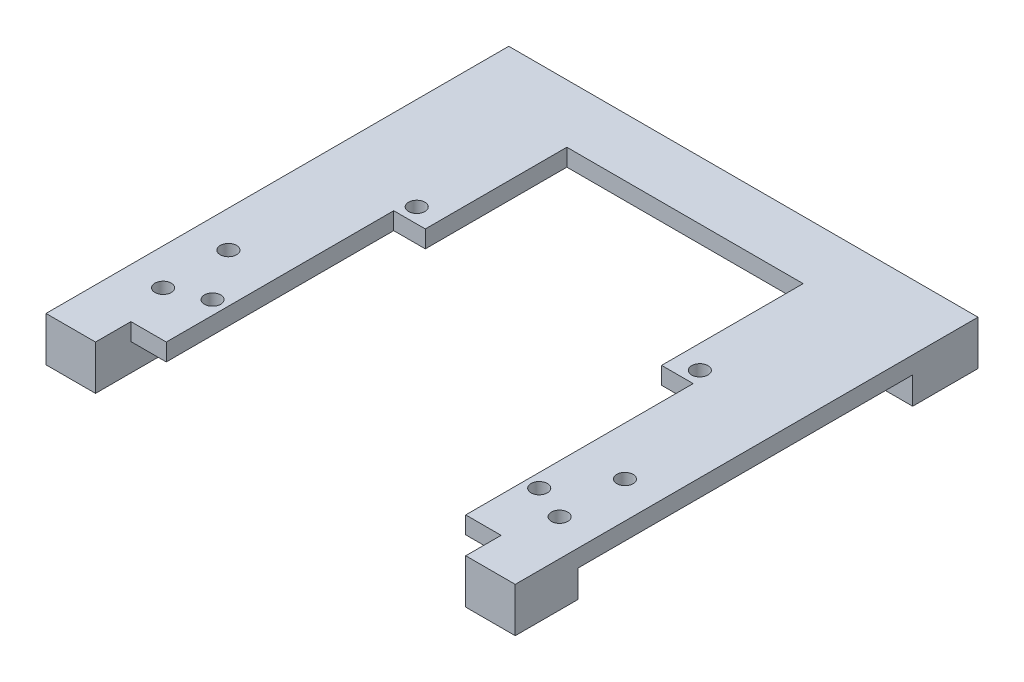
SolidWorks part; units mm, degrees
material "6061 Alloy"
ref_plane "Front Plane" through (0, 0, 0) normal (0, 0, 1) x (1, 0, 0)
ref_plane "Top Plane" through (0, 0, 0) normal (0, 1, 0) x (1, 0, 0)
ref_plane "Right Plane" through (0, 0, 0) normal (1, 0, 0) x (0, 0, -1)
sketch "Sketch1" plane through (0, 0, 0) normal (0, 1, 0) x (1, 0, 0)
  line L0 (0, 0) -> (0, -58.55) construction
  line L1 (-83.4462, -16.178) -> (-71.2857, -8.5793) construction
  line L6 (0, 0) -> (-59.046, 61.1439) construction
  line L7 (0, 0) -> (-72.0841, -45.0431) construction
  line L8 (-33.174, 78.2591) -> (-23.2129, 67.9442) construction
  line L9 (-72.0841, -45.0431) -> (-70.388, -43.9833) construction
  line L10 (-70.388, -43.9833) -> (-84.9608, -20.662) construction
  line L11 (-84.9608, -20.662) -> (-72.2401, -12.7132) construction
  line L12 (-72.2401, -12.7132) -> (-43.0945, -59.3558) construction
  line L13 (-43.0945, -59.3558) -> (-55.8152, -67.3046) construction
  line L14 (-55.8152, -67.3046) -> (-70.388, -43.9833) construction
  line L21 (-59.046, 61.1439) -> (-57.6566, 59.7052)
  line L22 (-77.4385, 40.6021) -> (-37.8748, 78.8083) construction
  line L23 (-73.9694, 32.6911) -> (-77.0537, 35.885)
  line L24 (-37.8748, 78.8083) -> (-27.4549, 68.0182) construction
  line L25 (-27.4549, 68.0182) -> (-67.0186, 29.812) construction
  line L26 (-67.0186, 29.812) -> (-77.4385, 40.6021) construction
  line L27 (-43.0945, -64.8266) -> (-34, -64.8266)
  line L33 (-86.5505, -18.1178) -> (-71.2857, -8.5793) construction
  line L34 (0, 0) -> (0, 50000) construction
  line L35 (0, 0) -> (-50000, 0) construction
  line L36 (-61.619, -58.55) -> (0, -58.55) construction
  line L38 (-67.0927, 25.57) -> (-79.5965, 38.5181) construction
  line L39 (-54.9774, -64.8266) -> (0, -64.8266) construction
  line L40 (-35.7168, 80.8923) -> (-23.2129, 67.9442) construction
  line L41 (-38.9606, -60.3102) -> (-54.2255, -69.8488) construction
  line L42 (-34, -58.55) -> (34, -58.55) construction
  line L43 (-43.0945, -64.8266) -> (-43.0945, -58.4123)
  line L45 (73.9694, 32.6911) -> (77.0537, 35.885)
  line L46 (-71.2857, -8.5793) -> (-38.9606, -60.3102) construction
  line L47 (83.4462, -16.178) -> (79.6809, -13.8252)
  line L48 (69.4846, -16.1792) -> (43.0945, -58.4123)
  line L49 (43.0945, -64.8266) -> (43.0945, -58.4123)
  line L50 (43.0945, -64.8266) -> (34, -64.8266)
  line L51 (34, -58.55) -> (34, -64.8266)
  line L52 (0, 0) -> (72.0841, -45.0431) construction
  line L53 (0, 0) -> (59.046, 61.1439) construction
  line L54 (-30.0897, 75.0653) -> (-30.2847, 63.8954)
  line L55 (-62.7996, 32.4961) -> (-30.2847, 63.8954)
  line L56 (-30.0897, 75.0653) -> (-33.174, 78.2591)
  line L57 (73.9694, 32.6911) -> (77.0537, 35.885)
  line L58 (30.0897, 75.0653) -> (33.174, 78.2591)
  line L59 (-34, -58.55) -> (-34, -53.55)
  line L60 (62.7996, 32.4961) -> (30.2847, 63.8954)
  line L61 (-73.9694, 32.6911) -> (-62.7996, 32.4961)
  line L62 (-77.0537, 35.885) -> (-67.0927, 25.57) construction
  line L63 (-83.4462, -16.178) -> (-79.6809, -13.8252)
  line L64 (-79.6809, -13.8252) -> (-69.4846, -16.1792)
  line L65 (-69.4846, -16.1792) -> (-43.0945, -58.4123)
  line L66 (-27.4549, 68.0182) -> (-23.2129, 67.9442) construction
  line L67 (-72.2401, -12.7132) -> (-71.2857, -8.5793) construction
  line L68 (30.0897, 75.0653) -> (30.2847, 63.8954)
  line L69 (73.9694, 32.6911) -> (62.7996, 32.4961)
  line L70 (-34, -58.55) -> (-34, -64.8266)
  line L71 (79.6809, -13.8252) -> (69.4846, -16.1792)
  line L72 (-34, -53.55) -> (-28, -53.55)
  line L73 (-28, -53.55) -> (-28, -58.55)
  line L74 (-28, -58.55) -> (28, -58.55)
  line L75 (28, -53.55) -> (28, -58.55)
  line L76 (34, -53.55) -> (28, -53.55)
  line L77 (34, -58.55) -> (34, -53.55)
  line L78 (-34, -58.55) -> (-28, -58.55)
  line L79 (28, -58.55) -> (34, -58.55)
  line L97 (-23.2129, 67.9442) -> (-67.0927, 25.57) construction
  circle A0 centre (0, 0) radius 85 construction
  circle A1 centre (0, 0) radius 90 construction
  arc A51 (-77.0537, 35.885) -> (-83.4462, -16.178) centre (0, 0) ccw
  arc A52 (77.0537, 35.885) -> (83.4462, -16.178) centre (0, 0) cw
  arc A54 (-33.174, 78.2591) -> (33.174, 78.2591) centre (0, 0) cw
  point P29 (-31.6318, 76.6622)
  point P33 (-47.2368, 48.9151)
  point P34 (31.6318, 76.6622)
  point P35 (-57.6673, -36.0345)
  point P85 (-57.6566, 59.7052)
  dimension "D2" = 58
  dimension "D12" = 170
  dimension "D14" = 34
  dimension "D15" = 3
  dimension "D3" = 180
  dimension "D4" = 64.8266
  dimension "D5" = 44
  dimension "D6" = 15
  dimension "D7" = 55
  dimension "D8" = 58.55
  dimension "D9" = 2
  dimension "D11" = 2
  dimension "D16" = 7
  dimension "D17" = 7
  dimension "D18" = 0.5
  dimension "D19" = 1
  dimension "D20" = 6
  dimension "D21" = 5
extrude "Boss-Extrude4" add sketch "Sketch1" along normal blind 3.175 contours A0 L70 | L59 L78 L73 L72 | L75 L79 L77 L76 region at (0, 0, -6.6852) region at (-31, 0, 56.05) region at (31, 0, 56.05)
ref_point "Rear_Axle_Center (L)"
ref_axis "Rear_Axle_Proj (L)" through (46.5421, 0, -48.1958) along (0, 1, 0)
ref_point "Front_Axle_Center (L)"
ref_axis "Front_Axle_Proj (L)" through (57.2432, 0, 35.7696) along (0, 1, 0)
ref_point "Front_Axle_Center (R)"
ref_axis "Front_Axle_Proj (R)" through (-57.2432, 0, 35.7696) along (0, 1, 0)
ref_point "Read_Axle_Center (R)"
ref_axis "Rear_Axle_Proj (R)" through (-46.5421, 0, -48.1958) along (0, 1, 0)
sketch "Sketch17" plane through (0, 3.175, 0) normal (0, 1, 0) x (1, 0, 0)
  line L0 (0, -53.55) -> (0, -58.55) construction
  line L1 (-34, -58.55) -> (34, -58.55) construction
  circle A0 centre (0, -53.55) radius 8.5
  dimension "D1" = 17
  dimension "D2" = 5
extrude "Boss-Extrude5" [suppressed] add sketch "Sketch17" against normal up to surface (3.175 mm away)
ref_plane "Plane1" through (0, 0, 10) normal (0, 0, 1) x (1, 0, 0)
hole_wizard "M3 Clearance Hole3" positions "Sketch18" profile "Sketch19" hole size "M3" standard "ANSI Metric" end condition through all
sketch "Sketch18" plane through (0, 0, 0) normal (0, -1, 0) x (-1, 0, 0)
  line L0 (-36.415, -50) -> (-36.415, -38) construction
  line L3 (0, 0) -> (0, -38) construction
  line L4 (36.415, -50) -> (36.415, -38) construction
  line L6 (0, -38) -> (36.415, -38) construction
  line L8 (0, -38) -> (-36.415, -38) construction
  point P1 (36.415, -50)
  point P3 (36.415, -38)
  point P5 (-36.415, -50)
  point P33 (-36.415, -38)
  dimension "D1" = 12
  dimension "D2" = 36.415
  dimension "D3" = 36.415
  dimension "D4" = 38
sketch "Sketch19" plane through (-36.415, 0, 50) normal (1, 0, 0) x (0, 0, -1)
  line L0 (0, 0) -> (0, 3.175)
  line L1 (0, 3.175) -> (1.5, 3.175)
  line L2 (1.5, 3.175) -> (1.5, 0)
  line L5 (1.5, 0) -> (0, 0)
  line L11 (0, -6.35) -> (0, 107.95) construction
  dimension "Thru Hole Dia." = 3
  dimension "Thru Hole Depth" = 3.175
hole_wizard "M3 Clearance Hole1" positions "Sketch11" profile "Sketch12" hole size "M3" standard "ANSI Metric" end condition through all
sketch "Sketch11" plane through (0, 3.175, 0) normal (0, 1, 0) x (1, 0, 0)
  line L0 (83.4462, -16.178) -> (79.6809, -13.8252) construction
  line L2 (73.9694, 32.6911) -> (77.0537, 35.885) construction
  line L4 (-73.9694, 32.6911) -> (-77.0537, 35.885) construction
  line L6 (0, 0) -> (0, -50000) construction
  line L7 (78.4111, 9.6277) -> (84.3664, 10.3589) construction
  line L10 (74.155, 27.2403) -> (78.5423, -8.4914) construction
  line L12 (78.4111, 9.6277) -> (76.3487, 9.3744) construction
  arc A7 (77.964, -12.7523) -> (72.563, 31.2347) centre (0, 0) ccw construction
  arc A13 (-77.964, -12.7523) -> (-72.563, 31.2347) centre (0, 0) cw construction
  arc A17 (83.4462, -16.178) -> (77.0537, 35.885) centre (0, 0) ccw construction
  point P34 (78.5423, -8.4914)
  point P66 (74.155, 27.2403)
  point P70 (-74.155, 27.2403)
  point P71 (-78.5423, -8.4914)
  dimension "D1" = 6
  dimension "D2" = 36
sketch "Sketch12" plane through (-78.5423, 3.175, 8.4914) normal (1, 0, 0) x (0, 0, 1)
  line L0 (0, 0) -> (0, 3.175)
  line L1 (0, 3.175) -> (1.55, 3.175)
  line L2 (1.55, 3.175) -> (1.55, 0)
  line L5 (1.55, 0) -> (0, 0)
  line L11 (0, -6.35) -> (0, 107.95) construction
  dimension "Thru Hole Dia." = 3.1
  dimension "Thru Hole Depth" = 3.175
hole_wizard "M3 Clearance Hole4" positions "Sketch9" profile "Sketch10" hole size "M3" standard "ANSI Metric" end condition through all
sketch "Sketch9" plane through (0, 0, 0) normal (0, -1, 0) x (-1, 0, 0)
  line L0 (0, 0) -> (0, 63.4318) construction
  line L1 (-38.0437, 52.9272) -> (38.0437, 52.9272) construction
  line L3 (61.0625, 30.6981) -> (-61.0625, 30.6981) construction
  line L4 (-67.0993, -15.2789) -> (67.0993, -15.2789) construction
  line L5 (50.1419, -42.4164) -> (-50.1419, -42.4164) construction
  line L6 (-61.0625, 30.6981) -> (-38.0437, 52.9272) construction
  line L7 (38.0437, 52.9272) -> (61.0625, 30.6981) construction
  line L8 (67.0993, -15.2789) -> (50.1419, -42.4164) construction
  line L9 (-50.1419, -42.4164) -> (-67.0993, -15.2789) construction
  line L10 (0, 0) -> (-44.8055, 46.3974) construction
  line L11 (0, 0) -> (44.8055, 46.3974) construction
  line L12 (0, 0) -> (-96.9468, 0) construction
  line L14 (-55.1231, -34.4448) -> (0, 0) construction
  line L15 (0, 0) -> (55.1231, -34.4448) construction
  line L18 (-69.4846, -16.1792) -> (-43.0945, -58.4123) construction
  line L19 (-62.7996, 32.4961) -> (-30.2847, 63.8954) construction
  point P0 (-67.0993, -15.2789)
  point P2 (-50.1419, -42.4164)
  point P9 (-61.0625, 30.6981)
  point P11 (-38.0437, 52.9272)
  point P30 (50.1419, -42.4164)
  point P31 (67.0993, -15.2789)
  point P32 (38.0437, 52.9272)
  point P33 (61.0625, 30.6981)
  dimension "D9" = 46
  dimension "D10" = 46
  dimension "D11" = 32
  dimension "D12" = 32
  dimension "D7" = 58
  dimension "D5" = 32
  dimension "D6" = 2.5
  dimension "D8" = 9.4
  dimension "D2" = 44
  dimension "D3" = 32
  dimension "D4" = 2.5
  dimension "D13" = 9.4
sketch "Sketch10" plane through (67.0993, 0, 15.2789) normal (1, 0, 0) x (0, 0, -1)
  line L0 (0, 0) -> (0, 3.175)
  line L1 (0, 3.175) -> (1.475, 3.175)
  line L2 (1.475, 3.175) -> (1.475, 0)
  line L5 (1.475, 0) -> (0, 0)
  line L11 (0, -6.35) -> (0, 107.95) construction
  dimension "Thru Hole Dia." = 2.95
  dimension "Thru Hole Depth" = 3.175
hole_wizard "M3 Clearance Hole2" positions "Sketch13" profile "Sketch14" hole size "M3" standard "ANSI Metric" end condition through all
sketch "Sketch13" plane through (0, 3.175, 0) normal (0, 1, 0) x (1, 0, 0)
  line L0 (0, 0) -> (0, 85) construction
  line L2 (-24, 47) -> (-24, 81) construction
  line L3 (-24, 47) -> (24, 47) construction
  line L4 (-24, 81) -> (24, 81) construction
  line L5 (24, 47) -> (24, 81) construction
  line L6 (-24, 47) -> (24, 81) construction
  line L7 (-24, 81) -> (24, 47) construction
  line L8 (-38.0437, 52.9272) -> (-61.0625, 30.6981) construction
  line L10 (-36.307, 51.1289) -> (-59.3259, 28.8998) construction
  line L11 (-16.3488, 39.8187) -> (-31.6313, 55.6441) construction
  line L12 (-16.3488, 39.8187) -> (-48.7191, 8.559) construction
  line L13 (-31.6313, 55.6441) -> (-64.0016, 24.3845) construction
  line L14 (-48.7191, 8.559) -> (-64.0016, 24.3845) construction
  line L15 (-16.3488, 39.8187) -> (-64.0016, 24.3845) construction
  line L16 (-31.6313, 55.6441) -> (-48.7191, 8.559) construction
  line L17 (-49.5531, 41.8127) -> (-40.1752, 32.1016) construction
  line L18 (-27, 76.4978) -> (-27, 80.5978) construction
  arc A0 (33.174, 78.2591) -> (-33.174, 78.2591) centre (0, 0) ccw construction
  circle A1 centre (-16.2162, 44) radius 3 construction
  circle A2 centre (-27, 76.4978) radius 3 construction
  point P65 (0, 64)
  point P181 (-27, 76.4978)
  point P184 (27, 76.4978)
  dimension "D7" = 6
  dimension "D1" = 48
  dimension "D2" = 34
  dimension "D3" = 4
  dimension "D5" = 45
  dimension "D6" = 22
  dimension "D8" = 4.1
  dimension "D4" = 2.5
sketch "Sketch14" plane through (27, 3.175, -76.4978) normal (1, 0, 0) x (0, 0, 1)
  line L0 (0, 0) -> (0, 3.175)
  line L1 (0, 3.175) -> (1.55, 3.175)
  line L2 (1.55, 3.175) -> (1.55, 0)
  line L5 (1.55, 0) -> (0, 0)
  line L11 (0, -6.35) -> (0, 107.95) construction
  dimension "Thru Hole Dia." = 3.1
  dimension "Thru Hole Depth" = 3.175
sketch "Sketch20" plane through (0, 3.175, 0) normal (0, 1, 0) x (1, 0, 0)
  line L0 (-16.1485, 45.5) -> (-16.1485, 40.5) construction
  line L1 (-14.6485, 45.5) -> (-14.6485, 40.5)
  line L2 (-17.6485, 45.5) -> (-17.6485, 40.5)
  line L3 (0, 0) -> (0, 85) construction
  line L5 (16.1485, 45.5) -> (16.1485, 40.5) construction
  line L6 (14.6485, 45.5) -> (14.6485, 40.5)
  line L7 (17.6485, 45.5) -> (17.6485, 40.5)
  arc A0 (-14.6485, 45.5) -> (-17.6485, 45.5) centre (-16.1485, 45.5) ccw
  arc A1 (-17.6485, 40.5) -> (-14.6485, 40.5) centre (-16.1485, 40.5) ccw
  arc A5 (33.174, 78.2591) -> (-33.174, 78.2591) centre (0, 0) ccw construction
  arc A7 (14.6485, 45.5) -> (17.6485, 45.5) centre (16.1485, 45.5) cw
  arc A8 (17.6485, 40.5) -> (14.6485, 40.5) centre (16.1485, 40.5) cw
  point P2 (-16.1485, 43)
  point P16 (16.1485, 43)
  dimension "D1" = 45.5
  dimension "D2" = 3
  dimension "D3" = 5
  dimension "D4" = 16.1485
extrude "Cut-Extrude1" cut sketch "Sketch20" against normal through all
sketch "Sketch22" plane through (0, 3.175, 0) normal (0, 1, 0) x (1, 0, 0)
  line L0 (-56.2896, -37.2958) -> (-57.6464, -38.1436) construction
  line L1 (-69.4846, -16.1792) -> (-43.0945, -58.4123) construction
  line L2 (-43.0945, -64.8266) -> (-43.0945, -58.4123) construction
  line L3 (30.2452, 66.1578) -> (65.062, 32.5356)
  line L4 (71.6894, -15.6702) -> (43.0945, -61.4316)
  line L28 (-30.2452, 66.1578) -> (-65.062, 32.5356)
  line L29 (-71.6894, -15.6702) -> (-43.0945, -61.4316)
  line L30 (-79.6809, -13.8252) -> (-69.4846, -16.1792) construction
  line L31 (0, 85) -> (0, -53.55) construction
  line L32 (-46.5421, 48.1958) -> (-47.6536, 49.3467) construction
  line L56 (-34, -58.55) -> (34, -58.55)
  line L60 (34, -58.55) -> (34, -64.8266)
  line L61 (34, -64.8266) -> (43.0945, -64.8266)
  line L62 (43.0945, -64.8266) -> (43.0945, -58.4123)
  line L63 (43.0945, -58.4123) -> (69.4846, -16.1792)
  line L64 (69.4846, -16.1792) -> (79.6809, -13.8252)
  line L65 (79.6809, -13.8252) -> (83.4462, -16.178)
  line L66 (77.0537, 35.885) -> (73.9694, 32.6911)
  line L67 (73.9694, 32.6911) -> (62.7996, 32.4961)
  line L68 (62.7996, 32.4961) -> (30.2847, 63.8954)
  line L69 (30.2847, 63.8954) -> (30.0897, 75.0653)
  line L70 (30.0897, 75.0653) -> (33.174, 78.2591)
  line L71 (-33.174, 78.2591) -> (-30.0897, 75.0653)
  line L72 (-30.0897, 75.0653) -> (-30.2847, 63.8954)
  line L73 (-30.2847, 63.8954) -> (-62.7996, 32.4961)
  line L74 (-62.7996, 32.4961) -> (-73.9694, 32.6911)
  line L75 (-73.9694, 32.6911) -> (-77.0537, 35.885)
  line L76 (-83.4462, -16.178) -> (-79.6809, -13.8252)
  line L77 (-79.6809, -13.8252) -> (-69.4846, -16.1792)
  line L78 (-69.4846, -16.1792) -> (-43.0945, -58.4123)
  line L79 (-43.0945, -58.4123) -> (-43.0945, -64.8266)
  line L80 (-43.0945, -64.8266) -> (-34, -64.8266)
  line L81 (-34, -64.8266) -> (-34, -58.55)
  line L84 (-34, -58.55) -> (34, -58.55)
  line L88 (34, -58.55) -> (34, -64.8266)
  line L89 (34, -64.8266) -> (43.0945, -64.8266)
  line L90 (43.0945, -64.8266) -> (43.0945, -58.4123)
  line L91 (43.0945, -58.4123) -> (69.4846, -16.1792)
  line L92 (69.4846, -16.1792) -> (79.6809, -13.8252)
  line L93 (79.6809, -13.8252) -> (83.4462, -16.178)
  line L94 (77.0537, 35.885) -> (73.9694, 32.6911)
  line L95 (73.9694, 32.6911) -> (62.7996, 32.4961)
  line L96 (62.7996, 32.4961) -> (30.2847, 63.8954)
  line L97 (30.2847, 63.8954) -> (30.0897, 75.0653)
  line L98 (30.0897, 75.0653) -> (33.174, 78.2591)
  line L99 (-33.174, 78.2591) -> (-30.0897, 75.0653)
  line L100 (-30.0897, 75.0653) -> (-30.2847, 63.8954)
  line L101 (-30.2847, 63.8954) -> (-62.7996, 32.4961)
  line L102 (-62.7996, 32.4961) -> (-73.9694, 32.6911)
  line L103 (-73.9694, 32.6911) -> (-77.0537, 35.885)
  line L104 (-83.4462, -16.178) -> (-79.6809, -13.8252)
  line L105 (-79.6809, -13.8252) -> (-69.4846, -16.1792)
  line L106 (-69.4846, -16.1792) -> (-43.0945, -58.4123)
  line L107 (-43.0945, -58.4123) -> (-43.0945, -64.8266)
  line L108 (-43.0945, -64.8266) -> (-34, -64.8266)
  line L109 (-34, -64.8266) -> (-34, -58.55)
  arc A9 (83.4462, -16.178) -> (77.0537, 35.885) centre (0, 0) ccw
  arc A10 (33.174, 78.2591) -> (-33.174, 78.2591) centre (0, 0) ccw
  arc A11 (-77.0537, 35.885) -> (-83.4462, -16.178) centre (0, 0) ccw
  arc A13 (83.4462, -16.178) -> (77.0537, 35.885) centre (0, 0) ccw
  arc A14 (33.174, 78.2591) -> (-33.174, 78.2591) centre (0, 0) ccw
  arc A15 (-77.0537, 35.885) -> (-83.4462, -16.178) centre (0, 0) ccw
  dimension "D2" = 1.6
  dimension "D1" = 0
extrude "Boss-Extrude6" add sketch "Sketch22" against normal up to surface (3.175 mm away) contours L102 L101 L100 L28 | L107 L106 L105 L29 | L92 L91 L90 L4 | L97 L96 L95 L3 region at (47.1042, 3.175, -48.7778) region at (-47.1042, 3.175, -48.7778) region at (56.8481, 3.175, 37.9317) region at (-56.8481, 3.175, 37.9317) up to face at (-16.1485, 0, -43)
fillet "Fillet1" [suppressed] radius 2
fillet "Fillet3" [suppressed] radius 1
sketch "Sketch23" [suppressed] plane through (0, 3.175, 0) normal (0, 1, 0) x (1, 0, 0)
  circle A0 centre (0, -53.55) radius 4.95
  dimension "D1" = 9.9
extrude "Cut-Extrude2" [suppressed] cut sketch "Sketch23" against normal through all
sketch "Sketch24" plane through (0, 3.175, 0) normal (0, 1, 0) x (1, 0, 0)
  line L0 (0, -58.55) -> (0, 85) construction
  line L1 (-34, -58.55) -> (34, -58.55) construction
  line L2 (-27, -52.75) -> (-27, -22.75)
  line L5 (0, 1.45) -> (-21.2, 1.45)
  line L9 (0, 1.45) -> (21.2, 1.45)
  line L11 (-27, -22.75) -> (-21.2, -22.75)
  line L13 (-21.2, -58.55) -> (-21.2, -52.75)
  line L14 (-21.2, -52.75) -> (-27, -52.75)
  line L17 (21.2, -58.55) -> (21.2, -52.75)
  line L18 (21.2, -52.75) -> (27, -52.75)
  line L20 (27, -52.75) -> (27, -22.75)
  line L21 (27, -22.75) -> (21.2, -22.75)
  line L22 (-21.2, -22.75) -> (-21.2, 1.45)
  line L23 (21.2, -58.55) -> (-21.2, -58.55)
  line L24 (21.2, -22.75) -> (21.2, 1.45)
  arc A0 (33.174, 78.2591) -> (-33.174, 78.2591) centre (0, 0) ccw construction
  point P23 (0, -58.55)
  dimension "D1" = 42.4
  dimension "D2" = 5.8
  dimension "D3" = 60
  dimension "D4" = 5.8
  dimension "D5" = 5.8
  dimension "D6" = 5.8
  dimension "D7" = 5.8
  dimension "D8" = 30
  dimension "D9" = 30
  dimension "D10" = 5.8
extrude "Cut-Extrude3" cut sketch "Sketch24" against normal through all
sketch "Sketch25" plane through (0, 3.175, 0) normal (0, 1, 0) x (1, 0, 0)
  line L0 (-21.2, -55.65) -> (-24.1, -55.65) construction
  line L1 (-21.2, -52.75) -> (-21.2, -58.55) construction
  line L2 (-24.1, -22.75) -> (-24.1, -19.85) construction
  line L4 (-21.2, -22.75) -> (-27, -22.75) construction
  line L5 (24.1, -22.75) -> (24.1, -19.85) construction
  line L6 (27, -22.75) -> (21.2, -22.75) construction
  line L7 (21.2, -55.65) -> (24.1, -55.65) construction
  line L8 (21.2, -58.55) -> (21.2, -52.75) construction
  circle A1 centre (-24.1, -55.65) radius 1.5
  circle A2 centre (-24.1, -19.85) radius 1.5
  circle A3 centre (24.1, -19.85) radius 1.5
  circle A4 centre (24.1, -55.65) radius 1.5
  dimension "D2" = 3
  dimension "D4" = 3
  dimension "D6" = 3
  dimension "D8" = 3
  dimension "D1" = 2.9
  dimension "D3" = 2.9
  dimension "D5" = 2.9
  dimension "D7" = 2.9
extrude "Cut-Extrude4" cut sketch "Sketch25" against normal through all
sketch "Sketch26" plane through (0, 3.175, 0) normal (0, 1, 0) x (1, 0, 0)
  line L4 (21.2, -58.55) -> (27.5, -58.55) construction
  line L5 (21.2, -58.55) -> (34, -58.55) construction
  line L6 (-27.5, -58.55) -> (27.5, -58.55)
  line L7 (-27.5, -58.55) -> (-27.5, 1.45)
  line L12 (-21.2, -58.55) -> (-27.5, -58.55) construction
  line L13 (-34, -58.55) -> (-21.2, -58.55) construction
  line L14 (27.5, -58.55) -> (27.5, 1.45)
  line L15 (-27.5, 1.45) -> (27.5, 1.45)
  dimension "D1" = 6.3
  dimension "D2" = 6.3
  dimension "D3" = 60
extrude "Cut-Extrude5" cut sketch "Sketch26" against normal blind 10
sketch "Sketch27" plane through (0, 3.175, 0) normal (0, 1, 0) x (1, 0, 0)
  line L0 (-43.0945, -64.8266) -> (43.0945, -64.8266)
  line L1 (-43.0945, -64.8266) -> (-43.0945, 20.1734)
  line L2 (43.0945, -64.8266) -> (43.0945, 20.1734)
  line L3 (-43.0945, 20.1734) -> (43.0945, 20.1734)
  dimension "D1" = 85
extrude "Cut-Extrude6" cut sketch "Sketch27" against normal blind 10 flip side to cut
sketch "Sketch32" plane through (0, 3.175, 0) normal (0, 1, 0) x (1, 0, 0)
  line L0 (-34, -64.8266) -> (34, -64.8266)
  line L1 (-34, -64.8266) -> (-34, -53.3266)
  line L2 (34, -64.8266) -> (34, -53.3266)
  line L3 (-34, -53.3266) -> (34, -53.3266)
  dimension "D1" = 11.5
extrude "Cut-Extrude9" cut sketch "Sketch32" against normal through all
sketch "Sketch33" plane through (0, 0, 0) normal (0, -1, 0) x (1, 0, 0)
  line L1 (-43.0945, 64.8266) -> (-34, 64.8266)
  line L2 (-43.0945, 64.8266) -> (-43.0945, 53.3266)
  line L3 (-43.0945, 53.3266) -> (-34, 53.3266)
  line L4 (-34, 64.8266) -> (-34, 53.3266)
  line L5 (43.0945, 64.8266) -> (34, 64.8266)
  line L6 (43.0945, 64.8266) -> (43.0945, 53.3266)
  line L7 (43.0945, 53.3266) -> (34, 53.3266)
  line L8 (34, 64.8266) -> (34, 53.3266)
  line L9 (-43.0945, -20.1734) -> (-35.0945, -20.1734)
  line L10 (-43.0945, -20.1734) -> (-43.0945, -8.1734)
  line L11 (-43.0945, -8.1734) -> (-35.0945, -8.1734)
  line L12 (-35.0945, -20.1734) -> (-35.0945, -8.1734)
  line L13 (43.0945, -20.1734) -> (35.0945, -20.1734)
  line L14 (43.0945, -20.1734) -> (43.0945, -8.1734)
  line L15 (43.0945, -8.1734) -> (35.0945, -8.1734)
  line L16 (35.0945, -20.1734) -> (35.0945, -8.1734)
  dimension "D1" = 8
  dimension "D2" = 12
  dimension "D3" = 8
  dimension "D4" = 12
extrude "Boss-Extrude7" add sketch "Sketch33" along normal blind 5
sketch "Sketch34" plane through (0, 0, 53.3266) normal (0, 0, 1) x (1, 0, 0)
  line L1 (-34, 0) -> (-27.5, 0)
  line L2 (-34, 0) -> (-34, 3.175)
  line L3 (-34, 3.175) -> (-27.5, 3.175)
  line L4 (-27.5, 0) -> (-27.5, 3.175)
  line L5 (34, 0) -> (27.5, 0)
  line L6 (34, 0) -> (34, 3.175)
  line L7 (34, 3.175) -> (27.5, 3.175)
  line L8 (27.5, 0) -> (27.5, 3.175)
extrude "Boss-Extrude8" add sketch "Sketch34" along normal blind 5
sketch "Sketch35" plane through (0, 3.175, 0) normal (0, 1, 0) x (1, 0, 0)
  line L0 (-27.5, -58.3266) -> (-27.5, -47.3266) construction
  line L1 (-27.5, 1.45) -> (-27.5, -58.3266) construction
  line L2 (-27.5, -47.3266) -> (-30, -47.3266) construction
  line L3 (27.5, -58.3266) -> (27.5, -47.3266) construction
  line L4 (27.5, -58.3266) -> (27.5, 1.45) construction
  line L5 (27.5, -47.3266) -> (30, -47.3266) construction
  circle A0 centre (-30, -47.3266) radius 1.5
  circle A1 centre (30, -47.3266) radius 1.5
  dimension "D3" = 3
  dimension "D6" = 3
  dimension "D1" = 11
  dimension "D2" = 2.5
  dimension "D4" = 11
  dimension "D5" = 2.5
extrude "Cut-Extrude10" cut sketch "Sketch35" against normal through all
sketch "Sketch37" plane through (0, 3.175, 0) normal (0, 1, 0) x (1, 0, 0)
  line L0 (-30, -47.3266) -> (-30, -13.8266) construction
  line L1 (-30, -13.8266) -> (-26, -13.8266) construction
  line L2 (30, -47.3266) -> (30, -13.8266) construction
  line L3 (30, -13.8266) -> (26, -13.8266) construction
  circle A0 centre (-26, -13.8266) radius 1.5
  circle A1 centre (26, -13.8266) radius 1.5
  dimension "D3" = 3
  dimension "D6" = 3
  dimension "D1" = 33.5
  dimension "D2" = 4
  dimension "D4" = 33.5
  dimension "D5" = 4
sketch "Sketch38" plane through (-27.5, 0, 0) normal (1, 0, 0) x (0, 0, -1)
  line L0 (1.45, 3.175) -> (-58.3266, 3.175) construction
  line L1 (1.45, 0) -> (-16.55, 0)
  line L2 (1.45, 0) -> (1.45, 3.175)
  line L3 (1.45, 3.175) -> (-16.55, 3.175)
  line L4 (-16.55, 0) -> (-16.55, 3.175)
  dimension "D1" = 18
extrude "Boss-Extrude10" add sketch "Sketch38" along normal blind 5.8
sketch "Sketch39" plane through (27.5, 0, 0) normal (-1, 0, 0) x (0, 0, 1)
  line L0 (58.3266, 3.175) -> (-1.45, 3.175) construction
  line L1 (-1.45, 0) -> (16.55, 0)
  line L2 (-1.45, 0) -> (-1.45, 3.175)
  line L3 (-1.45, 3.175) -> (16.55, 3.175)
  line L4 (16.55, 0) -> (16.55, 3.175)
  dimension "D1" = 18
extrude "Boss-Extrude11" add sketch "Sketch39" along normal blind 5.8
extrude "Cut-Extrude14" cut sketch "Sketch37" against normal through all
sketch "Sketch40" plane through (0, 3.175, 0) normal (0, 1, 0) x (1, 0, 0)
  line L0 (-21.7, 1.45) -> (21.7, 1.45)
  line L1 (-21.7, 1.45) -> (-21.7, 9.45)
  line L2 (21.7, 1.45) -> (21.7, 9.45)
  line L3 (-21.7, 9.45) -> (21.7, 9.45)
  dimension "D1" = 8
extrude "Cut-Extrude15" cut sketch "Sketch40" against normal through all
equation "\"D3@Sketch18\"=\"D2@Sketch18\""
equation "\"D2@Sketch18\"=72.83/2"
equation "\"D3@Sketch9\"=\"D5@Sketch9\""
equation "\"D4@Sketch9\"=\"D6@Sketch9\""
equation "\"D13@Sketch9\"=\"D8@Sketch9\""
